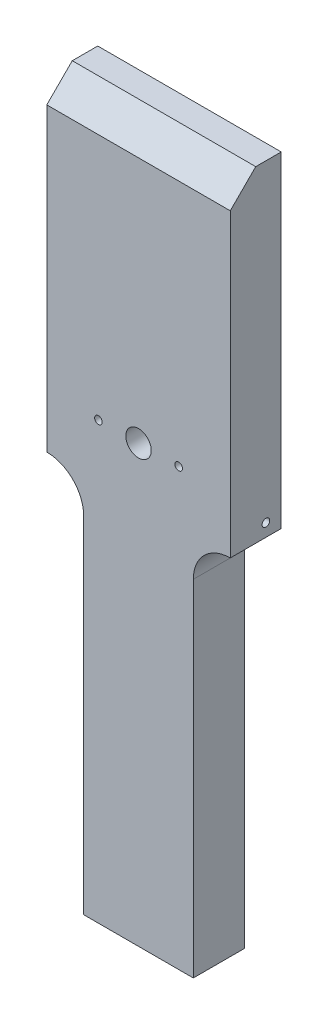
SolidWorks part; units mm, degrees
ref_plane "Front Plane" through (0, 0, 0) normal (0, 0, 1) x (1, 0, 0)
ref_plane "Top Plane" through (0, 0, 0) normal (0, 1, 0) x (1, 0, 0)
ref_plane "Right Plane" through (0, 0, 0) normal (1, 0, 0) x (0, 0, -1)
sketch "Sketch1" plane through (0, 0, 0) normal (0, 0, 1) x (1, 0, 0)
  line L0 (0, 0) -> (0, -50000) construction
  line L1 (114.3, 203.2) -> (-114.3, 203.2)
  line L2 (114.3, 203.2) -> (114.3, -203.2)
  line L3 (114.3, -203.2) -> (-114.3, -203.2)
  line L4 (-114.3, 203.2) -> (-114.3, -203.2)
  line L5 (114.3, 203.2) -> (-114.3, -203.2) construction
  line L6 (114.3, -203.2) -> (-114.3, 203.2) construction
  line L7 (-68.2625, -679.45) -> (68.2625, -679.45)
  line L8 (-68.2625, -679.45) -> (-68.2625, -203.2)
  line L9 (-68.2625, -203.2) -> (68.2625, -203.2)
  line L10 (68.2625, -679.45) -> (68.2625, -203.2)
  line L11 (-68.2625, -679.45) -> (68.2625, -203.2) construction
  line L12 (-68.2625, -203.2) -> (68.2625, -679.45) construction
  line L13 (-49.9584, -136.525) -> (49.9584, -136.525) construction
  circle A0 centre (0, -136.525) radius 15.875
  circle A1 centre (-49.9584, -136.525) radius 4.7625
  circle A2 centre (49.9584, -136.525) radius 4.7625
  point P0 (0, 0)
  point P6 (0, -441.325)
  point P17 (0, -136.525)
  point P20 (-49.9584, -71.053)
  dimension "D5" = 31.75
  dimension "D6" = 9.525
  dimension "D1" = 136.525
  dimension "D2" = 476.25
  dimension "D3" = 406.4
  dimension "D4" = 228.6
  dimension "D7" = 66.675
extrude "Boss-Extrude1" add sketch "Sketch1" along normal blind 63.5 contours L7 L10 L3 L8 | L4 L3 L2 L1 | A0 | A1 | A2 region at (0, -441.325, 0)
sketch "Sketch2" plane through (0, 0, 0) normal (0, 0, -1) x (-1, 0, 0)
  line L0 (0, 0) -> (0, -50000) construction
  line L1 (68.2625, -679.45) -> (-68.2625, -679.45) construction
  line L2 (-19.05, -165.1) -> (19.05, -165.1)
  line L3 (-19.05, -165.1) -> (-19.05, -660.4)
  line L4 (-19.05, -660.4) -> (19.05, -660.4)
  line L5 (19.05, -165.1) -> (19.05, -660.4)
  line L6 (-19.05, -165.1) -> (19.05, -660.4) construction
  line L7 (-19.05, -660.4) -> (19.05, -165.1) construction
  point P3 (0, -412.75)
  dimension "D1" = 38.1
  dimension "D2" = 495.3
  dimension "D3" = 19.05
extrude "Cut-Extrude1" cut sketch "Sketch2" against normal blind 36.5125
sketch "Sketch3" plane through (-114.3, 0, 0) normal (-1, 0, 0) x (0, 0, 1)
  line L0 (0, 203.2) -> (0, -203.2) construction
  line L6 (0, -165.1) -> (0, -660.4)
  line L7 (0, -660.4) -> (36.5125, -660.4)
  line L8 (36.5125, -660.4) -> (36.5125, -165.1)
  line L9 (36.5125, -165.1) -> (0, -165.1)
  line L10 (0, -165.1) -> (0, -660.4)
  line L11 (0, -660.4) -> (36.5125, -660.4)
  line L12 (36.5125, -660.4) -> (36.5125, -165.1)
  line L13 (36.5125, -165.1) -> (0, -165.1)
  circle A0 centre (19.05, -187.325) radius 4.7625
  dimension "D4" = 9.525
  dimension "D1" = 19.05
  dimension "D2" = 0
  dimension "D3" = 22.225
extrude "Cut-Extrude2" cut sketch "Sketch3" against normal through all contours A0 region at (-114.3, -187.325, 19.05)
fillet "Fillet1" radius 46.0375 2 edges at (68.2625, -203.2, 31.75) (-68.2625, -203.2, 31.75)
chamfer "Chamfer1" distance 31.75 angle 45 1 edges at (0, 203.2, 63.5)
